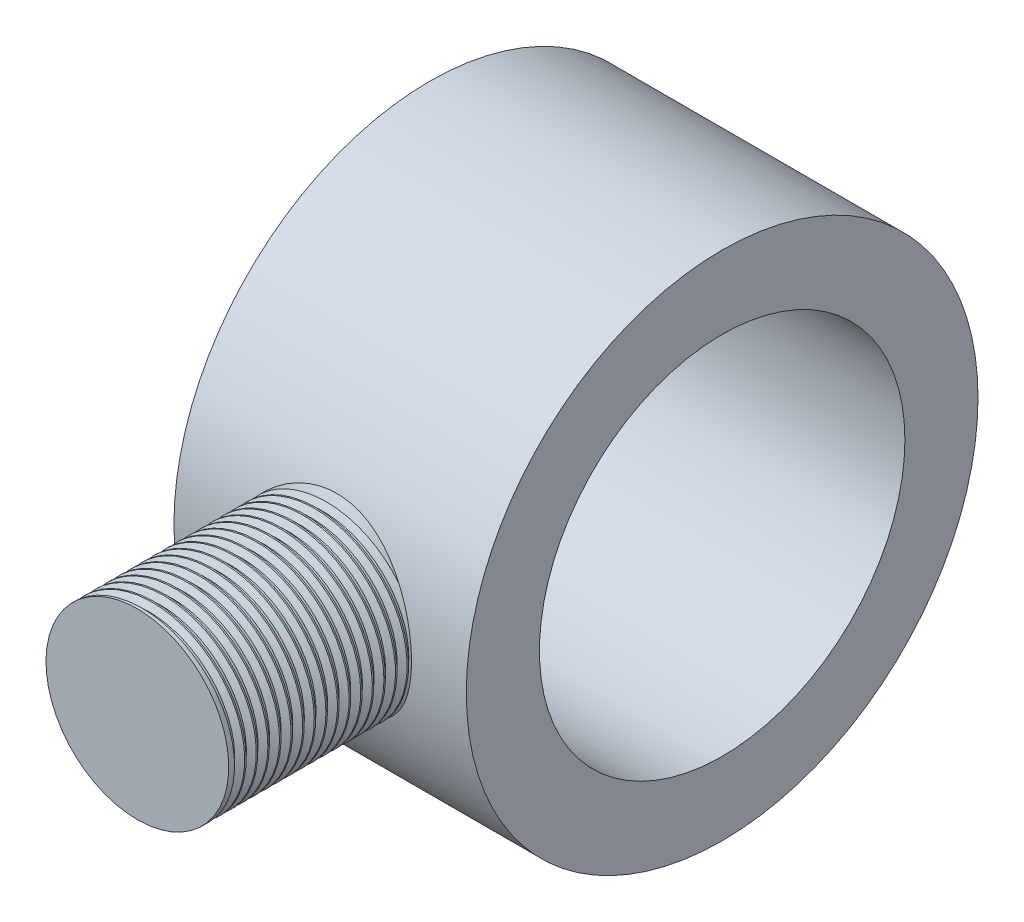
SolidWorks part; units mm, degrees
ref_plane "Front Plane" through (0, 0, 0) normal (0, 0, 1) x (1, 0, 0)
ref_plane "Top Plane" through (0, 0, 0) normal (0, 1, 0) x (1, 0, 0)
ref_plane "Right Plane" through (0, 0, 0) normal (1, 0, 0) x (0, 0, -1)
sketch "Sketch1" plane through (0, 0, 0) normal (1, 0, 0) x (0, 0, -1)
  circle A0 centre (0, 0) radius 7
  dimension "D1" = 14
extrude "Boss-Extrude1" add sketch "Sketch1" along normal blind 8
sketch "Sketch2" plane through (8, 0, 0) normal (1, 0, 0) x (0, 0, -1)
  circle A0 centre (0, 0) radius 5
  dimension "D1" = 10
extrude "Cut-Extrude1" cut sketch "Sketch2" against normal through all
ref_plane "Plane1" through (0, 0, 7) normal (0, 0, 1) x (1, 0, 0)
sketch "Sketch3" plane through (0, 0, 7) normal (0, 0, 1) x (1, 0, 0)
  line L0 (8, 0) -> (0, 0) construction
  circle A0 centre (4, 0) radius 2.5
  dimension "D1" = 5
  dimension "D2" = 0
  dimension "D3" = 4
extrude "Boss-Extrude3" add sketch "Sketch3" against normal blind 1
sketch "Sketch4" plane through (0, 0, 7) normal (0, 0, 1) x (1, 0, 0)
  circle A0 centre (4, 0) radius 2.5
  dimension "D1" = 5
  dimension "D2" = 4
extrude "Boss-Extrude4" add sketch "Sketch4" along normal blind 5
thread "Thread1" pitch 0.3175 method cut profile "Thread Profile1" start angle 1, offset 0, length 5, pitch 0.3175, diameter 5
ref_plane "Plane2" through (1.5004, 0.0436, 12) normal (-0.0175, -0.9998, 0) x (-0.9998, 0.0175, 0)
sketch "Thread Profile1" plane through (1.5004, 0.0436, 12) normal (-0.0175, -0.9998, 0) x (-0.9998, 0.0175, 0)
  line L0 (0, 0) -> (0, 0.3175) construction
  line L11 (0, 0) -> (0, 0.2778)
  line L12 (0, 0.2778) -> (-0.1719, 0.1786)
  line L13 (-0.1719, 0.1786) -> (-0.1719, 0.0992)
  line L15 (-0.1719, 0.0992) -> (0, 0)
  line L17 (-0.1719, 0.1389) -> (0, 0.1389) construction
  point P2 (0, 0)
  dimension "Pitch" = 0.3175
  dimension "Profile_Angle" = 60
  dimension "Profile_Land" = 0.0794
  dimension "Profile_Height" = 0.1719
